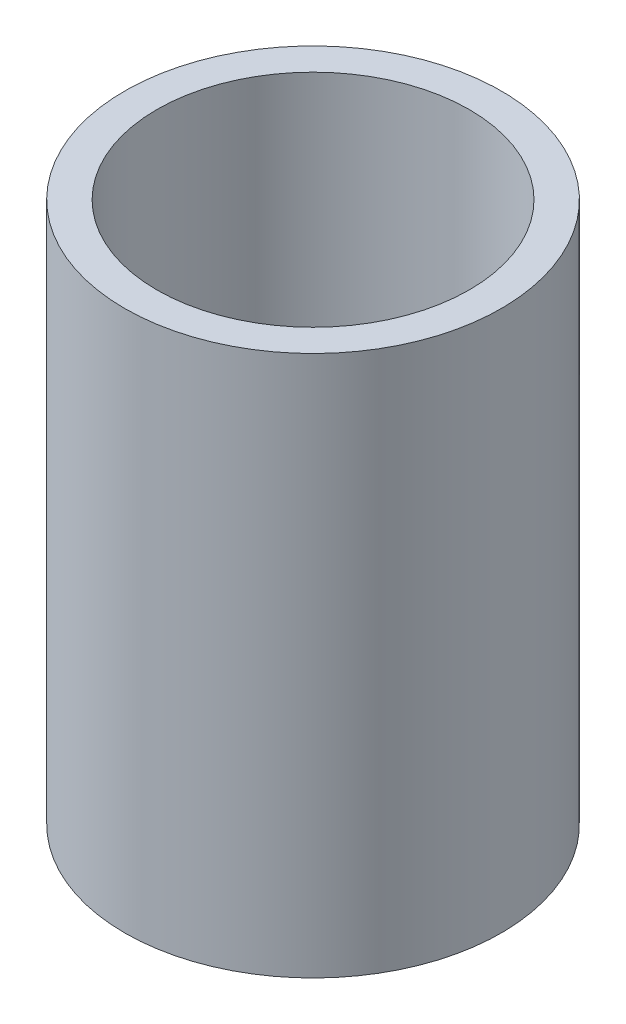
SolidWorks part; units mm, degrees
ref_plane "Front Plane" through (0, 0, 0) normal (0, 0, 1) x (1, 0, 0)
ref_plane "Top Plane" through (0, 0, 0) normal (0, 1, 0) x (1, 0, 0)
ref_plane "Right Plane" through (0, 0, 0) normal (1, 0, 0) x (0, 0, -1)
sketch "Sketch1" plane through (0, 0, 0) normal (0, 1, 0) x (1, 0, 0)
  circle A0 centre (0, 0) radius 25
  dimension "SLEEVE_OD" = 50
extrude "Boss-Extrude1" add sketch "Sketch1" along normal blind 71.7825
sketch "Sketch2" plane through (0, 0, 0) normal (0, 1, 0) x (1, 0, 0)
  circle A0 centre (0, 0) radius 20.7379
  dimension "BORE_D" = 41.4757
extrude "Cut-Extrude1" cut sketch "Sketch2" along normal through all
chamfer "Chamfer1" distance 3.1211 angle 60 rebuild error yes
